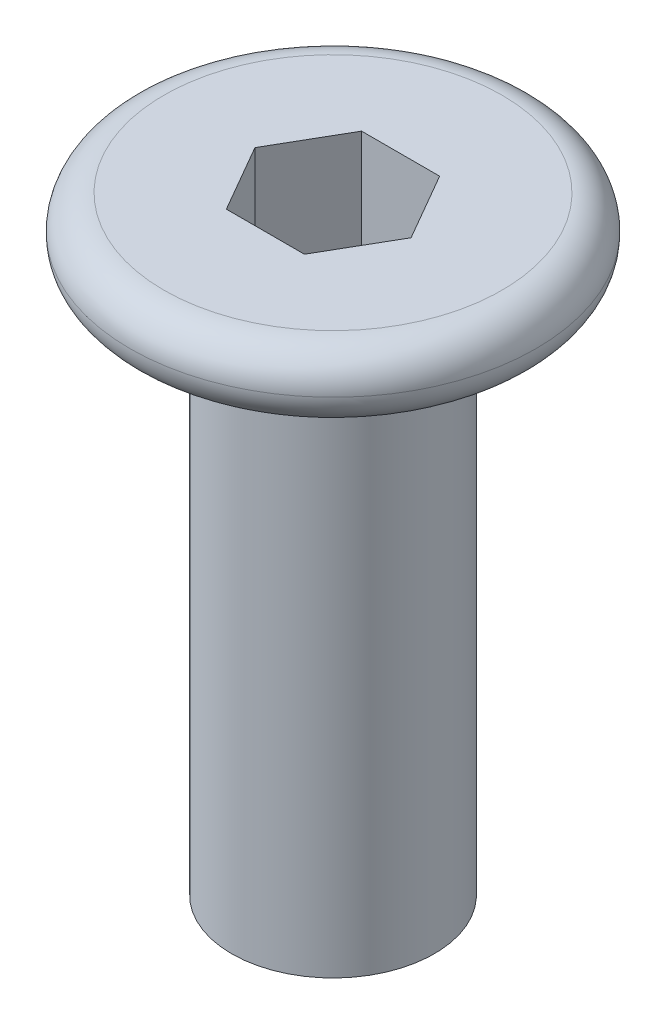
SolidWorks part; units mm, degrees
material "AISI 304"
ref_plane "前视基准面" through (0, 0, 0) normal (0, 0, 1) x (1, 0, 0)
ref_plane "上视基准面" through (0, 0, 0) normal (0, 1, 0) x (1, 0, 0)
ref_plane "右视基准面" through (0, 0, 0) normal (1, 0, 0) x (0, 0, -1)
other "Configuration Table"
sketch "草图1" plane through (0, 0, 0) normal (0, 1, 0) x (1, 0, 0)
  circle A0 centre (0, 0) radius 3
  dimension "D1" = 6
extrude "凸台-拉伸1" add sketch "草图1" along normal blind 1
sketch "草图2" plane through (0, 0, 0) normal (0, -1, 0) x (1, 0, 0)
  circle A0 centre (0, 0) radius 1.5
  dimension "D1" = 3
extrude "凸台-拉伸2" add sketch "草图2" along normal blind 8
sketch "草图3" plane through (0, 1, 0) normal (0, 1, 0) x (1, 0, 0)
  line L1 (0.5774, -1) -> (1.1547, 0)
  line L2 (1.1547, 0) -> (0.5774, 1)
  line L3 (0.5774, 1) -> (-0.5774, 1)
  line L4 (-0.5774, 1) -> (-1.1547, 0)
  line L5 (-1.1547, 0) -> (-0.5774, -1)
  line L6 (-0.5774, -1) -> (0.5774, -1)
  circle A0 centre (0, 0) radius 1 construction
  dimension "D1" = 2
extrude "切除-拉伸1" cut sketch "草图3" against normal blind 2
fillet "圆角1" radius 0.5 2 edges at (0, 0, 3) (0, 1, 3)
